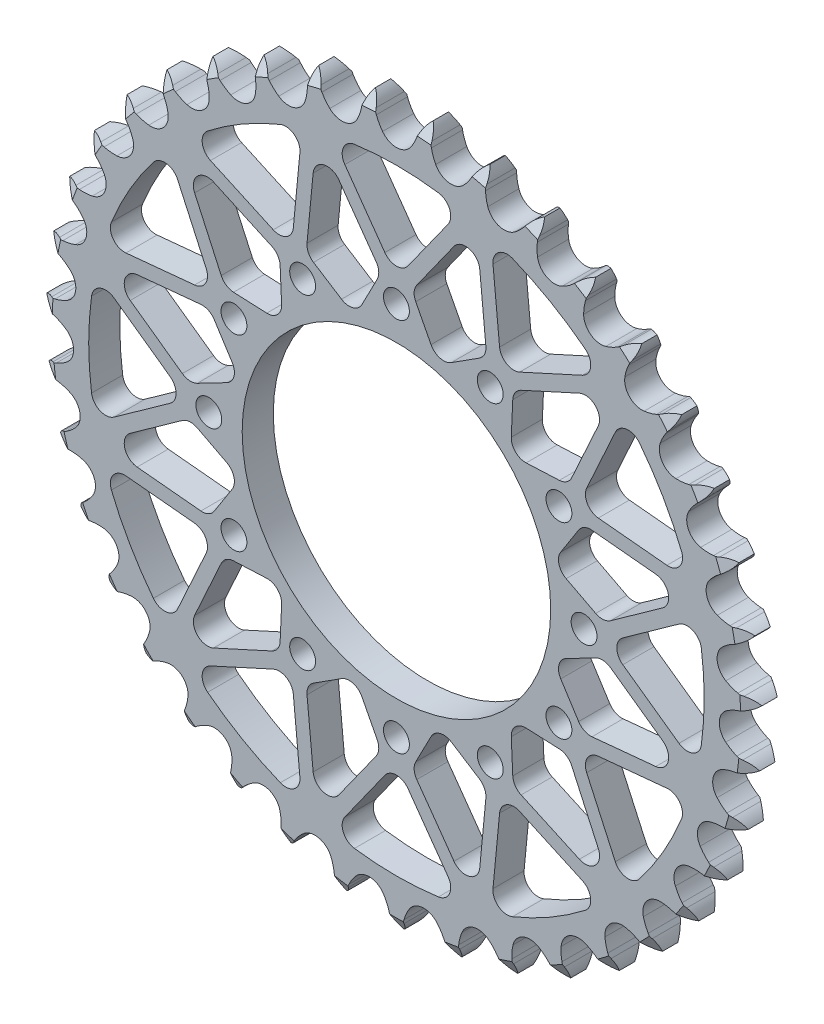
SolidWorks part; units mm, degrees
material "7075-T6 (SN)"
ref_plane "Front Plane" through (0, 0, 0) normal (0, 0, 1) x (1, 0, 0)
ref_plane "Top Plane" through (0, 0, 0) normal (0, 1, 0) x (1, 0, 0)
ref_plane "Right Plane" through (0, 0, 0) normal (1, 0, 0) x (0, 0, -1)
sketch "Work Sketch" plane through (0, 0, 0) normal (0, 0, 1) x (1, 0, 0)
  line L0 (0, 0) -> (0, 160.4542) construction
  line L1 (-112.0919, 78.9148) -> (87.2579, 78.9148) construction
  line L2 (5.102, 120.8822) -> (5.102, 112.9699) construction
  line L3 (-12.8497, 82.6953) -> (16.7256, 82.6953) construction
  line L4 (5.102, 82.6953) -> (-6.0879, 74.4036) construction
  line L5 (5.102, 82.6953) -> (-4.6505, 79.1506) construction
  line L6 (-4.6505, 79.1506) -> (-6.8863, 85.3019)
  line L7 (-11.5114, 78.0206) -> (-7.1525, 78.0206) construction
  line L8 (-11.0765, 124.7602) -> (-11.0765, 110.2345) construction
  line L9 (0, 0) -> (-3.4402, 42.6146) construction
  circle A0 centre (0, 0) radius 78.9148
  circle A1 centre (0, 78.9148) radius 4.0088
  arc A2 (-4.6505, 79.1506) -> (-3.2209, 76.5281) centre (5.0804, 82.7541) ccw
  circle A3 centre (-11.0765, 78.0206) radius 6.4254
  point P23 (-3.2209, 76.5281)
  dimension "D1" = 157.8295
  dimension "D8" = 10.3767
  dimension "D2" = 8.0177
  dimension "D3" = 5.102
  dimension "D4" = 3.7806
  dimension "D5" = 36.538
  dimension "D6" = 16.564
  dimension "D7" = 10.3767
  dimension "D9" = 0.8942
  dimension "D10" = 11.0765
  dimension "D11" = 4.615
sketch "Teeth Sketch" plane through (0, 0, 0) normal (0, 0, 1) x (1, 0, 0)
  line L0 (5.0376, 80.2155) -> (4.6505, 79.1506)
  line L1 (-7.4865, 92.7372) -> (-4.7839, 59.2593) construction
  line L2 (0, 0) -> (-10.9133, 132.3061) construction
  line L3 (7.8951, 79.9848) -> (8.1063, 78.8717)
  line L4 (16093.3137, -199351.4616) -> (-16096.7539, 199394.0762) construction
  line L5 (0, 146.3285) -> (0, 56.9858) construction
  line L6 (17.8398, 78.3686) -> (17.287, 77.3797)
  line L7 (0, -200000) -> (0, 200160.4542) construction
  line L8 (20.6234, 77.6826) -> (20.6533, 76.5499)
  line L9 (-4.6505, 79.1506) -> (-6.8863, 85.3019) construction
  line L10 (44.1616, 67.154) -> (43.8313, 66.0702)
  line L11 (-5.0376, 80.2155) -> (-4.6505, 79.1506)
  line L12 (30.18, 74.4921) -> (29.4757, 73.6046)
  line L13 (32.8175, 73.3684) -> (32.6653, 72.2456)
  line L14 (41.7385, 68.6862) -> (40.901, 67.9232)
  line L15 (52.2161, 61.1014) -> (51.267, 60.4826)
  line L16 (54.362, 59.2003) -> (53.8621, 58.1836)
  line L17 (61.3413, 51.9341) -> (60.3052, 51.4756)
  line L18 (63.1544, 49.7134) -> (62.4979, 48.79)
  line L19 (68.8777, 41.4218) -> (67.7815, 41.1354)
  line L20 (70.3112, 38.939) -> (69.515, 38.1328)
  line L21 (74.6303, 29.8366) -> (73.5023, 29.7298)
  line L22 (75.6469, 27.156) -> (74.7318, 26.488)
  line L23 (78.45, 17.4787) -> (77.3195, 17.5542)
  line L24 (79.0234, 14.6698) -> (78.013, 14.1572)
  line L25 (80.2378, 4.6681) -> (79.1341, 4.9239)
  line L26 (80.3533, 1.8035) -> (79.2737, 1.4597)
  line L27 (79.9476, -8.2634) -> (78.8992, -7.8338)
  line L28 (79.602, -11.1094) -> (78.4813, -11.2756)
  line L29 (77.5867, -20.9809) -> (76.6208, -20.3887)
  line L30 (76.7891, -23.7346) -> (75.6562, -23.7189)
  line L31 (73.2164, -33.155) -> (72.358, -32.4155)
  line L32 (71.9874, -35.7451) -> (70.8717, -35.5478)
  line L33 (66.9499, -44.4704) -> (66.2212, -43.6028)
  line L34 (65.3213, -46.8298) -> (64.2517, -46.4561)
  line L35 (58.9493, -54.634) -> (58.3693, -53.6608)
  line L36 (56.9634, -56.7016) -> (55.9676, -56.1612)
  line L37 (49.422, -63.3827) -> (49.0056, -62.329)
  line L38 (47.1301, -65.1049) -> (46.2339, -64.4118)
  line L39 (38.6147, -70.4897) -> (38.3727, -69.3829)
  line L40 (36.0763, -71.822) -> (35.3028, -70.9941)
  line L41 (26.8073, -75.7712) -> (26.746, -74.6398)
  line L42 (24.088, -76.679) -> (23.4574, -75.7377)
  line L43 (14.3056, -79.0901) -> (14.4266, -77.9636)
  line L44 (11.4759, -79.55) -> (11.0044, -78.5198)
  line L45 (1.4334, -80.3607) -> (1.7335, -79.2682)
  line L46 (-1.4334, -80.3607) -> (-1.7335, -79.2682)
  line L47 (-11.4759, -79.55) -> (-11.0044, -78.5198)
  line L48 (-14.3056, -79.0901) -> (-14.4266, -77.9636)
  line L49 (-24.088, -76.679) -> (-23.4574, -75.7377)
  line L50 (-26.8073, -75.7712) -> (-26.746, -74.6398)
  line L51 (-36.0763, -71.822) -> (-35.3028, -70.9941)
  line L52 (-38.6147, -70.4897) -> (-38.3727, -69.3829)
  line L53 (-47.1301, -65.1049) -> (-46.2339, -64.4118)
  line L54 (-49.422, -63.3827) -> (-49.0056, -62.329)
  line L55 (-56.9634, -56.7016) -> (-55.9676, -56.1612)
  line L56 (-58.9493, -54.634) -> (-58.3693, -53.6608)
  line L57 (-65.3213, -46.8298) -> (-64.2517, -46.4561)
  line L58 (-66.9499, -44.4704) -> (-66.2212, -43.6028)
  line L59 (-71.9874, -35.7451) -> (-70.8717, -35.5478)
  line L60 (-73.2164, -33.155) -> (-72.358, -32.4155)
  line L61 (-76.7891, -23.7346) -> (-75.6562, -23.7189)
  line L62 (-77.5867, -20.9809) -> (-76.6208, -20.3887)
  line L63 (-79.602, -11.1094) -> (-78.4813, -11.2756)
  line L64 (-79.9476, -8.2634) -> (-78.8992, -7.8338)
  line L65 (-80.3533, 1.8035) -> (-79.2737, 1.4597)
  line L66 (-80.2378, 4.6681) -> (-79.1341, 4.9239)
  line L67 (-79.0234, 14.6698) -> (-78.013, 14.1572)
  line L68 (-78.45, 17.4787) -> (-77.3195, 17.5542)
  line L69 (-75.6469, 27.156) -> (-74.7318, 26.488)
  line L70 (-74.6303, 29.8366) -> (-73.5023, 29.7298)
  line L71 (-70.3112, 38.939) -> (-69.515, 38.1328)
  line L72 (-68.8777, 41.4218) -> (-67.7815, 41.1354)
  line L73 (-63.1544, 49.7134) -> (-62.4979, 48.79)
  line L74 (-61.3413, 51.9341) -> (-60.3052, 51.4756)
  line L75 (-54.362, 59.2003) -> (-53.8621, 58.1836)
  line L76 (-52.2161, 61.1014) -> (-51.267, 60.4826)
  line L77 (-44.1616, 67.154) -> (-43.8313, 66.0702)
  line L78 (-41.7385, 68.6862) -> (-40.901, 67.9232)
  line L79 (-32.8175, 73.3684) -> (-32.6653, 72.2456)
  line L80 (-30.18, 74.4921) -> (-29.4757, 73.6046)
  line L81 (-20.6234, 77.6826) -> (-20.6533, 76.5499)
  line L82 (-17.8398, 78.3686) -> (-17.287, 77.3797)
  line L83 (-7.8951, 79.9848) -> (-8.1063, 78.8717)
  arc A0 (-6.8336, 82.8459) -> (-5.0376, 80.2155) centre (-11.0765, 78.0206) cw
  circle A1 centre (-11.0765, 78.0206) radius 6.4254 construction
  arc A2 (-3.2209, 76.5281) -> (-4.6505, 79.1506) centre (5.0804, 82.7541) cw
  arc A3 (-4.6505, 79.1506) -> (-3.2209, 76.5281) centre (5.0804, 82.7541) ccw construction
  circle A4 centre (0, 78.9148) radius 4.0088 construction
  arc A5 (-3.2209, 76.5281) -> (3.2209, 76.5281) centre (0, 78.9148) ccw
  arc A6 (3.2209, 76.5281) -> (4.6505, 79.1506) centre (-5.0804, 82.7541) ccw
  arc A7 (6.8336, 82.8459) -> (5.0376, 80.2155) centre (11.0765, 78.0206) ccw
  arc A8 (6.5443, 82.8692) -> (7.8951, 79.9848) centre (1.5824, 78.787) cw
  arc A9 (9.0967, 76.0537) -> (8.1063, 78.8717) centre (18.2893, 80.8676) cw
  arc A10 (9.0967, 76.0537) -> (15.4552, 75.0204) centre (12.6588, 77.8928) ccw
  arc A11 (15.4552, 75.0204) -> (17.287, 77.3797) centre (8.2601, 82.4975) ccw
  arc A12 (20.0345, 80.6769) -> (17.8398, 78.3686) centre (23.4484, 75.2334) ccw
  arc A13 (19.7528, 80.7463) -> (20.6234, 77.6826) centre (14.2002, 77.5129) cw
  arc A14 (21.1788, 73.6096) -> (20.6533, 76.5499) centre (31.0245, 76.8865) cw
  arc A15 (21.1788, 73.6096) -> (27.2892, 71.5697) centre (24.9898, 74.8535) ccw
  arc A16 (27.2892, 71.5697) -> (29.4757, 73.6046) centre (21.3867, 80.1041) ccw
  arc A17 (32.7165, 76.4184) -> (30.18, 74.4921) centre (35.2131, 70.4978) ccw
  arc A18 (32.4496, 76.5321) -> (32.8175, 73.3684) centre (26.4502, 74.2313) cw
  arc A19 (32.7124, 69.2591) -> (32.6653, 72.2456) centre (42.9562, 70.9142) cw
  arc A20 (32.7124, 69.2591) -> (38.4163, 66.2654) centre (36.6735, 69.8756) ccw
  arc A21 (38.4163, 66.2654) -> (40.901, 67.9232) centre (33.9593, 75.6361) ccw
  arc A22 (44.5512, 70.1807) -> (41.7385, 68.6862) centre (46.0657, 63.9363) ccw
  arc A23 (44.306, 70.3358) -> (44.1616, 67.154) centre (38.0153, 69.0271) cw
  arc A24 (43.3987, 63.1147) -> (43.8313, 66.0702) centre (53.7754, 63.1052) cw
  arc A25 (43.3987, 63.1147) -> (48.5486, 59.2448) centre (47.4074, 63.0878) ccw
  arc A26 (48.5486, 59.2448) -> (51.267, 60.4826) centre (45.6524, 69.2092) ccw
  arc A27 (55.2321, 62.1253) -> (52.2161, 61.1014) centre (55.7253, 55.7189) ccw
  arc A28 (55.0149, 62.3178) -> (54.362, 59.2003) centre (48.5957, 62.0351) cw
  arc A29 (52.961, 55.3358) -> (53.8621, 58.1836) centre (63.2018, 53.6618) cw
  arc A30 (52.961, 55.3358) -> (57.4234, 50.6899) centre (56.9135, 54.6662) ccw
  arc A31 (57.4234, 50.6899) -> (60.3052, 51.4756) centre (56.1632, 60.9898) ccw
  arc A32 (64.4824, 52.461) -> (61.3413, 51.9341) centre (63.9416, 46.0584) ccw
  arc A33 (64.2989, 52.6858) -> (63.1544, 49.7134) centre (57.9175, 53.4365) cw
  arc A34 (61.1517, 46.1237) -> (62.4979, 48.79) centre (70.9913, 42.8287) cw
  arc A35 (61.1517, 46.1237) -> (64.811, 40.8221) centre (64.9456, 44.8287) ccw
  arc A36 (64.811, 40.8221) -> (67.7815, 41.1354) centre (65.2193, 51.1908) ccw
  arc A37 (72.0627, 41.4379) -> (68.8777, 41.4218) centre (70.5018, 35.205) ccw
  arc A38 (71.9177, 41.6892) -> (70.3112, 38.939) centre (65.7393, 43.4539) cw
  arc A39 (67.7585, 35.717) -> (69.515, 38.1328) centre (76.9422, 30.8862) cw
  arc A40 (67.7585, 35.717) -> (70.5201, 29.8971) centre (71.2956, 33.8302) ccw
  arc A41 (70.5201, 29.8971) -> (73.5023, 29.7298) centre (72.5864, 40.0659) ccw
  arc A42 (77.7767, 29.3416) -> (74.6303, 29.8366) centre (75.2361, 23.4398) ccw
  arc A43 (77.6738, 29.6129) -> (75.6469, 27.156) centre (71.8585, 32.3458) cw
  arc A44 (72.6105, 24.3852) -> (74.7318, 26.488) centre (80.9003, 18.1439) cw
  arc A45 (72.6105, 24.3852) -> (74.4027, 18.1977) centre (75.7991, 21.9555) ccw
  arc A46 (74.4027, 18.1977) -> (77.3195, 17.5542) centre (78.0734, 27.9034) ccw
  arc A47 (81.4762, 16.4854) -> (78.45, 17.4787) centre (78.0218, 11.0675) ccw
  arc A48 (81.4182, 16.7697) -> (79.0234, 14.6698) centre (76.1166, 20.4) cw
  arc A49 (75.5818, 12.4219) -> (78.013, 14.1572) centre (82.7631, 4.9316) cw
  arc A50 (75.5818, 12.4219) -> (76.3583, 6.027) centre (78.3394, 9.5121) ccw
  arc A51 (76.3583, 6.027) -> (79.1341, 4.9239) centre (81.5384, 15.0182) ccw
  arc A52 (83.0656, 3.2022) -> (80.2378, 4.6681) centre (78.7868, -1.5914) ccw
  arc A53 (83.0539, 3.4922) -> (80.3533, 1.8035) centre (78.4033, 7.9259) cw
  arc A54 (76.5957, 0.1368) -> (79.2737, 1.4597) centre (82.4825, -8.4084) cw
  arc A55 (76.5957, 0.1368) -> (76.3363, -6.2998) centre (78.8508, -3.1776) ccw
  arc A56 (76.3363, -6.2998) -> (78.8992, -7.8338) centre (82.8916, 1.7441) ccw
  arc A57 (82.5035, -10.1639) -> (79.9476, -8.2634) centre (77.5113, -14.2091) ccw
  arc A58 (82.5385, -9.8758) -> (79.602, -11.1094) centre (78.6594, -4.7535) cw
  arc A59 (75.6257, -12.1517) -> (78.4813, -11.2756) centre (80.0655, -21.5307) cw
  arc A60 (75.6257, -12.1517) -> (74.3372, -18.4634) centre (77.3199, -15.785) ccw
  arc A61 (74.3372, -18.4634) -> (76.6208, -20.3887) centre (82.0979, -11.5753) ccw
  arc A62 (79.8047, -23.2668) -> (77.5867, -20.9809) centre (74.2283, -26.4587) ccw
  arc A63 (79.8855, -22.9881) -> (76.7891, -23.7346) centre (76.8783, -17.3098) cw
  arc A64 (72.6971, -24.1256) -> (75.6562, -23.7189) centre (75.5749, -34.0953) cw
  arc A65 (72.6971, -24.1256) -> (70.4128, -30.1488) centre (73.7866, -27.9836) ccw
  arc A66 (70.4128, -30.1488) -> (72.358, -32.4155) centre (79.178, -24.5948) ccw
  arc A67 (75.039, -35.7671) -> (73.2164, -33.155) centre (69.0227, -38.0232) ccw
  arc A68 (75.1634, -35.5049) -> (71.9874, -35.7451) centre (73.106, -29.4178) cw
  arc A69 (67.8857, -35.4746) -> (70.8717, -35.5478) centre (69.127, -45.7768) cw
  arc A70 (67.8857, -35.4746) -> (64.6648, -41.0534) centre (68.3422, -39.4574) ccw
  arc A71 (64.6648, -41.0534) -> (66.2212, -43.6028) centre (74.2074, -36.9773) ccw
  arc A72 (68.3299, -47.341) -> (66.9499, -44.4704) centre (62.0296, -48.6028) ccw
  arc A73 (68.4947, -47.1022) -> (65.3213, -46.8298) centre (67.4404, -40.7639) cw
  arc A74 (61.3161, -45.9049) -> (64.2517, -46.4561) centre (60.8887, -56.2728) cw
  arc A75 (61.3161, -45.9049) -> (57.2419, -50.8948) centre (61.1278, -49.9093) ccw
  arc A76 (57.2419, -50.8948) -> (58.3693, -53.6608) centre (67.3148, -48.4022) ccw
  arc A77 (59.851, -57.6888) -> (58.9493, -54.634) centre (53.4299, -57.9236) ccw
  arc A78 (60.052, -57.4796) -> (56.9634, -56.7016) centre (60.0281, -51.0542) cw
  arc A79 (53.1584, -55.1462) -> (55.9676, -56.1612) centre (51.0734, -65.3113) cw
  arc A80 (53.1584, -55.1462) -> (48.3366, -59.4179) centre (52.3302, -59.0685) ccw
  arc A81 (48.3366, -59.4179) -> (49.0056, -62.329) centre (58.6789, -58.5735) ccw
  arc A82 (49.822, -66.5425) -> (49.422, -63.3827) centre (43.4464, -65.7443) ccw
  arc A83 (50.054, -66.3682) -> (47.1301, -65.1049) centre (51.0611, -60.0222) cw
  arc A84 (43.6239, -62.9593) -> (46.2339, -64.4118) centre (39.9354, -72.6583) cw
  arc A85 (43.6239, -62.9593) -> (38.1793, -66.4022) centre (42.1772, -66.698) ccw
  arc A86 (38.1793, -66.4022) -> (38.3727, -69.3829) centre (48.5231, -67.2277) ccw
  arc A87 (38.5026, -73.6728) -> (38.6147, -70.4897) centre (32.3376, -71.8622) ccw
  arc A88 (38.7596, -73.538) -> (36.0763, -71.822) centre (40.7716, -67.4357) cw
  arc A89 (32.9596, -69.1417) -> (35.3028, -70.9941) centre (27.763, -78.1234) cw
  arc A90 (32.9596, -69.1417) -> (27.0333, -71.6667) centre (30.932, -72.6) ccw
  arc A91 (27.0333, -71.6667) -> (26.746, -74.6398) centre (37.1107, -74.1408) ccw
  arc A92 (26.1861, -78.8951) -> (26.8073, -75.7712) centre (20.3913, -76.1189) ccw
  arc A93 (26.4613, -78.8032) -> (24.088, -76.679) centre (29.4261, -73.1027) cw
  arc A94 (21.4417, -73.5335) -> (23.4574, -75.7377) centre (14.8716, -81.5653) cw
  arc A95 (21.4417, -73.5335) -> (15.187, -75.0751) centre (18.8855, -76.6216) ccw
  arc A96 (15.187, -75.0751) -> (14.4266, -77.9636) centre (24.7371, -79.1336) ccw
  arc A97 (13.1913, -82.0739) -> (14.3056, -79.0901) centre (7.9169, -78.4042) ccw
  arc A98 (13.4777, -82.0274) -> (11.4759, -79.55) centre (17.3186, -76.8763) cw
  arc A99 (9.3684, -76.0207) -> (11.0044, -78.5198) centre (1.595, -82.8946) cw
  arc A100 (9.3684, -76.0207) -> (2.9475, -76.5391) centre (6.35, -78.6589) ccw
  arc A101 (2.9475, -76.5391) -> (1.7335, -79.2682) centre (11.7228, -82.077) ccw
  arc A102 (-0.1451, -83.1271) -> (1.4334, -80.3607) centre (-4.7625, -78.6589) ccw
  arc A103 (0.1451, -83.1271) -> (-1.4334, -80.3607) centre (4.7625, -78.6589) cw
  arc A104 (-2.9475, -76.5391) -> (-1.7335, -79.2682) centre (-11.7228, -82.077) cw
  arc A105 (-2.9475, -76.5391) -> (-9.3684, -76.0207) centre (-6.35, -78.6589) ccw
  arc A106 (-9.3684, -76.0207) -> (-11.0044, -78.5198) centre (-1.595, -82.8946) ccw
  arc A107 (-13.4777, -82.0274) -> (-11.4759, -79.55) centre (-17.3186, -76.8763) ccw
  arc A108 (-13.1913, -82.0739) -> (-14.3056, -79.0901) centre (-7.9169, -78.4042) cw
  arc A109 (-15.187, -75.0751) -> (-14.4266, -77.9636) centre (-24.7371, -79.1336) cw
  arc A110 (-15.187, -75.0751) -> (-21.4417, -73.5335) centre (-18.8855, -76.6216) ccw
  arc A111 (-21.4417, -73.5335) -> (-23.4574, -75.7377) centre (-14.8716, -81.5653) ccw
  arc A112 (-26.4613, -78.8032) -> (-24.088, -76.679) centre (-29.4261, -73.1027) ccw
  arc A113 (-26.1861, -78.8951) -> (-26.8073, -75.7712) centre (-20.3913, -76.1189) cw
  arc A114 (-27.0333, -71.6667) -> (-26.746, -74.6398) centre (-37.1107, -74.1408) cw
  arc A115 (-27.0333, -71.6667) -> (-32.9596, -69.1417) centre (-30.932, -72.6) ccw
  arc A116 (-32.9596, -69.1417) -> (-35.3028, -70.9941) centre (-27.763, -78.1234) ccw
  arc A117 (-38.7596, -73.538) -> (-36.0763, -71.822) centre (-40.7716, -67.4357) ccw
  arc A118 (-38.5026, -73.6728) -> (-38.6147, -70.4897) centre (-32.3376, -71.8622) cw
  arc A119 (-38.1793, -66.4022) -> (-38.3727, -69.3829) centre (-48.5231, -67.2277) cw
  arc A120 (-38.1793, -66.4022) -> (-43.6239, -62.9593) centre (-42.1772, -66.698) ccw
  arc A121 (-43.6239, -62.9593) -> (-46.2339, -64.4118) centre (-39.9354, -72.6583) ccw
  arc A122 (-50.054, -66.3682) -> (-47.1301, -65.1049) centre (-51.0611, -60.0222) ccw
  arc A123 (-49.822, -66.5425) -> (-49.422, -63.3827) centre (-43.4464, -65.7443) cw
  arc A124 (-48.3366, -59.4179) -> (-49.0056, -62.329) centre (-58.6789, -58.5735) cw
  arc A125 (-48.3366, -59.4179) -> (-53.1584, -55.1462) centre (-52.3302, -59.0685) ccw
  arc A126 (-53.1584, -55.1462) -> (-55.9676, -56.1612) centre (-51.0734, -65.3113) ccw
  arc A127 (-60.052, -57.4796) -> (-56.9634, -56.7016) centre (-60.0281, -51.0542) ccw
  arc A128 (-59.851, -57.6888) -> (-58.9493, -54.634) centre (-53.4299, -57.9236) cw
  arc A129 (-57.2419, -50.8948) -> (-58.3693, -53.6608) centre (-67.3148, -48.4022) cw
  arc A130 (-57.2419, -50.8948) -> (-61.3161, -45.9049) centre (-61.1278, -49.9093) ccw
  arc A131 (-61.3161, -45.9049) -> (-64.2517, -46.4561) centre (-60.8887, -56.2728) ccw
  arc A132 (-68.4947, -47.1022) -> (-65.3213, -46.8298) centre (-67.4404, -40.7639) ccw
  arc A133 (-68.3299, -47.341) -> (-66.9499, -44.4704) centre (-62.0296, -48.6028) cw
  arc A134 (-64.6648, -41.0534) -> (-66.2212, -43.6028) centre (-74.2074, -36.9773) cw
  arc A135 (-64.6648, -41.0534) -> (-67.8857, -35.4746) centre (-68.3422, -39.4574) ccw
  arc A136 (-67.8857, -35.4746) -> (-70.8717, -35.5478) centre (-69.127, -45.7768) ccw
  arc A137 (-75.1634, -35.5049) -> (-71.9874, -35.7451) centre (-73.106, -29.4178) ccw
  arc A138 (-75.039, -35.7671) -> (-73.2164, -33.155) centre (-69.0227, -38.0232) cw
  arc A139 (-70.4128, -30.1488) -> (-72.358, -32.4155) centre (-79.178, -24.5948) cw
  arc A140 (-70.4128, -30.1488) -> (-72.6971, -24.1256) centre (-73.7866, -27.9836) ccw
  arc A141 (-72.6971, -24.1256) -> (-75.6562, -23.7189) centre (-75.5749, -34.0953) ccw
  arc A142 (-79.8855, -22.9881) -> (-76.7891, -23.7346) centre (-76.8783, -17.3098) ccw
  arc A143 (-79.8047, -23.2668) -> (-77.5867, -20.9809) centre (-74.2283, -26.4587) cw
  arc A144 (-74.3372, -18.4634) -> (-76.6208, -20.3887) centre (-82.0979, -11.5753) cw
  arc A145 (-74.3372, -18.4634) -> (-75.6257, -12.1517) centre (-77.3199, -15.785) ccw
  arc A146 (-75.6257, -12.1517) -> (-78.4813, -11.2756) centre (-80.0655, -21.5307) ccw
  arc A147 (-82.5385, -9.8758) -> (-79.602, -11.1094) centre (-78.6594, -4.7535) ccw
  arc A148 (-82.5035, -10.1639) -> (-79.9476, -8.2634) centre (-77.5113, -14.2091) cw
  arc A149 (-76.3363, -6.2998) -> (-78.8992, -7.8338) centre (-82.8916, 1.7441) cw
  arc A150 (-76.3363, -6.2998) -> (-76.5957, 0.1368) centre (-78.8508, -3.1776) ccw
  arc A151 (-76.5957, 0.1368) -> (-79.2737, 1.4597) centre (-82.4825, -8.4084) ccw
  arc A152 (-83.0539, 3.4922) -> (-80.3533, 1.8035) centre (-78.4033, 7.9259) ccw
  arc A153 (-83.0656, 3.2022) -> (-80.2378, 4.6681) centre (-78.7868, -1.5914) cw
  arc A154 (-76.3583, 6.027) -> (-79.1341, 4.9239) centre (-81.5384, 15.0182) cw
  arc A155 (-76.3583, 6.027) -> (-75.5818, 12.4219) centre (-78.3394, 9.5121) ccw
  arc A156 (-75.5818, 12.4219) -> (-78.013, 14.1572) centre (-82.7631, 4.9316) ccw
  arc A157 (-81.4182, 16.7697) -> (-79.0234, 14.6698) centre (-76.1166, 20.4) ccw
  arc A158 (-81.4762, 16.4854) -> (-78.45, 17.4787) centre (-78.0218, 11.0675) cw
  arc A159 (-74.4027, 18.1977) -> (-77.3195, 17.5542) centre (-78.0734, 27.9034) cw
  arc A160 (-74.4027, 18.1977) -> (-72.6105, 24.3852) centre (-75.7991, 21.9555) ccw
  arc A161 (-72.6105, 24.3852) -> (-74.7318, 26.488) centre (-80.9003, 18.1439) ccw
  arc A162 (-77.6738, 29.6129) -> (-75.6469, 27.156) centre (-71.8585, 32.3458) ccw
  arc A163 (-77.7767, 29.3416) -> (-74.6303, 29.8366) centre (-75.2361, 23.4398) cw
  arc A164 (-70.5201, 29.8971) -> (-73.5023, 29.7298) centre (-72.5864, 40.0659) cw
  arc A165 (-70.5201, 29.8971) -> (-67.7585, 35.717) centre (-71.2956, 33.8302) ccw
  arc A166 (-67.7585, 35.717) -> (-69.515, 38.1328) centre (-76.9422, 30.8862) ccw
  arc A167 (-71.9177, 41.6892) -> (-70.3112, 38.939) centre (-65.7393, 43.4539) ccw
  arc A168 (-72.0627, 41.4379) -> (-68.8777, 41.4218) centre (-70.5018, 35.205) cw
  arc A169 (-64.811, 40.8221) -> (-67.7815, 41.1354) centre (-65.2193, 51.1908) cw
  arc A170 (-64.811, 40.8221) -> (-61.1517, 46.1237) centre (-64.9456, 44.8287) ccw
  arc A171 (-61.1517, 46.1237) -> (-62.4979, 48.79) centre (-70.9913, 42.8287) ccw
  arc A172 (-64.2989, 52.6858) -> (-63.1544, 49.7134) centre (-57.9175, 53.4365) ccw
  arc A173 (-64.4824, 52.461) -> (-61.3413, 51.9341) centre (-63.9416, 46.0584) cw
  arc A174 (-57.4234, 50.6899) -> (-60.3052, 51.4756) centre (-56.1632, 60.9898) cw
  arc A175 (-57.4234, 50.6899) -> (-52.961, 55.3358) centre (-56.9135, 54.6662) ccw
  arc A176 (-52.961, 55.3358) -> (-53.8621, 58.1836) centre (-63.2018, 53.6618) ccw
  arc A177 (-55.0149, 62.3178) -> (-54.362, 59.2003) centre (-48.5957, 62.0351) ccw
  arc A178 (-55.2321, 62.1253) -> (-52.2161, 61.1014) centre (-55.7253, 55.7189) cw
  arc A179 (-48.5486, 59.2448) -> (-51.267, 60.4826) centre (-45.6524, 69.2092) cw
  arc A180 (-48.5486, 59.2448) -> (-43.3987, 63.1147) centre (-47.4074, 63.0878) ccw
  arc A181 (-43.3987, 63.1147) -> (-43.8313, 66.0702) centre (-53.7754, 63.1052) ccw
  arc A182 (-44.306, 70.3358) -> (-44.1616, 67.154) centre (-38.0153, 69.0271) ccw
  arc A183 (-44.5512, 70.1807) -> (-41.7385, 68.6862) centre (-46.0657, 63.9363) cw
  arc A184 (-38.4163, 66.2654) -> (-40.901, 67.9232) centre (-33.9593, 75.6361) cw
  arc A185 (-38.4163, 66.2654) -> (-32.7124, 69.2591) centre (-36.6735, 69.8756) ccw
  arc A186 (-32.7124, 69.2591) -> (-32.6653, 72.2456) centre (-42.9562, 70.9142) ccw
  arc A187 (-32.4496, 76.5321) -> (-32.8175, 73.3684) centre (-26.4502, 74.2313) ccw
  arc A188 (-32.7165, 76.4184) -> (-30.18, 74.4921) centre (-35.2131, 70.4978) cw
  arc A189 (-27.2892, 71.5697) -> (-29.4757, 73.6046) centre (-21.3867, 80.1041) cw
  arc A190 (-27.2892, 71.5697) -> (-21.1788, 73.6096) centre (-24.9898, 74.8535) ccw
  arc A191 (-21.1788, 73.6096) -> (-20.6533, 76.5499) centre (-31.0245, 76.8865) ccw
  arc A192 (-19.7528, 80.7463) -> (-20.6234, 77.6826) centre (-14.2002, 77.5129) ccw
  arc A193 (-20.0345, 80.6769) -> (-17.8398, 78.3686) centre (-23.4484, 75.2334) cw
  arc A194 (-15.4552, 75.0204) -> (-17.287, 77.3797) centre (-8.2601, 82.4975) cw
  arc A195 (-15.4552, 75.0204) -> (-9.0967, 76.0537) centre (-12.6588, 77.8928) ccw
  arc A196 (-9.0967, 76.0537) -> (-8.1063, 78.8717) centre (-18.2893, 80.8676) ccw
  arc A197 (-6.5443, 82.8692) -> (-7.8951, 79.9848) centre (-1.5824, 78.787) ccw
  point P77 (0, 0)
  dimension "D1" = 4.615
  dimension "D2" = 4.715
  dimension "D3" = 39
extrude "Extrusion" add sketch "Teeth Sketch" along normal blind 7.2136 contours A0 region at (0, 0, 0)
sketch "Sketch1" plane through (0, 0, 0) normal (0, 0, -1) x (-1, 0, 0)
  circle A0 centre (0, 0) radius 78.9443
  circle A1 centre (0, 0) radius 35.7643
  dimension "D1" = 43.18
extrude "Cut-Extrude" cut sketch "Sketch1" against normal through all both and the other way through all contours A1
ref_axis "Axis2" through (0, 0, -0.3607) along (0, 0, 1)
ref_axis "Axis1" [suppressed] through (0, 0, 7.2136) along (0, 0, -1)
ref_plane "Sprocket Center Plane" through (0, 0, 3.6068) normal (0, 0, 1) x (1, 0, 0)
sketch "Pitch Circle" plane through (0, 0, 3.6068) normal (0, 0, -1) x (-1, 0, 0)
  circle A0 centre (0, 0) radius 82.9531 construction
  dimension "D1" = 165.9063
sketch "Chain Pitch Circle" plane through (0, 0, 0) normal (0, 0, -1) x (-1, 0, 0)
  circle A0 centre (0, 0) radius 82.9531 construction
  dimension "D1" = 165.9063
ref_plane "Center Plane" through (0, 0, 3.6068) normal (0, 0, 1) x (1, 0, 0)
hole_wizard "Ø6.0mm Dowel Hole1" positions "Sketch7" profile "Sketch8" hole size "Ø6.0" standard "ANSI Metric" end condition through all
sketch "Sketch7" plane through (0, 0, 7.2136) normal (0, 0, 1) x (1, 0, 0)
  point P0 (-43.5, 0)
  dimension "D1" = 43.5
sketch "Sketch8" plane through (-43.5, 0, 7.2136) normal (1, 0, 0) x (0, -1, 0)
  line L0 (0, 0) -> (0, 7.2136)
  line L1 (0, 7.2136) -> (3, 7.2136)
  line L2 (3, 7.2136) -> (3, 0)
  line L5 (3, 0) -> (0, 0)
  line L11 (0, -6.35) -> (0, 107.95) construction
  dimension "Thru Hole Dia." = 6
  dimension "Thru Hole Depth" = 7.2136
pattern_circular "CirPattern1" count 12 over 360 about axis through (0, 0, 7.2136) along (0, 0, -1) of "Ø6.0mm Dowel Hole1" reverse direction yes
ref_plane "Plane1" through (0, 0, 3.6068) normal (0, 0, -1) x (-1, 0, 0)
sketch "Sketch9" plane through (0, 0, 0) normal (0, 0, 1) x (1, 0, 0)
  line L0 (-43.5, 0) -> (-71.3499, 0) construction
  line L1 (-69.7539, 15.0068) -> (-48.707, 0)
  line L2 (-69.7539, -15.0068) -> (-48.707, 0)
  line L11 (-43.5, 0) -> (-37.6721, 21.75) construction
  line L13 (-68.9187, 18.4667) -> (-36.1404, 9.6838) construction
  line L18 (-43.3252, 20.9264) -> (-36.1404, 9.6838)
  line L19 (-47.9839, 3.5399) -> (-36.1404, 9.6838)
  line L20 (-43.3252, 20.9264) -> (-68.9187, 18.4667)
  line L21 (-47.9839, 3.5399) -> (-68.9187, 18.4667)
  circle A0 centre (0, 0) radius 74.9059 construction
  arc A1 (-57.4234, 50.6899) -> (-52.961, 55.3358) centre (-56.9135, 54.6662) ccw construction
  circle A2 centre (-43.5, 0) radius 3 construction
  circle A3 centre (-43.5, 0) radius 5.207
  circle A4 centre (-37.6721, 21.75) radius 3 construction
  circle A6 centre (-37.6721, 21.75) radius 5.207
  circle A196 centre (0, 0) radius 71.3499
  circle A197 centre (0, 0) radius 35.7643 construction
  circle A198 centre (0, 0) radius 35.7643
  circle A199 centre (0, 0) radius 37.4153 construction
  point P17 (-40.5861, 10.875)
  dimension "D1" = 3.556
  dimension "D2" = 1.651
  dimension "D3" = 10.414
  dimension "D4" = 3.302
extrude "Cut-Extrude2" cut sketch "Sketch9" along normal through all contours L1 A196 L2 | L21 L19 L18 L20 region at (-63.4426, 0, 0) region at (-50.2379, 13.4612, 0)
fillet "Fillet2" radius 3.302 7 edges at (-68.9187, 18.4667, 3.6068) (-36.1404, 9.6838, 3.6068) (-47.9839, 3.5399, 3.6068) (-43.3252, 20.9264, 3.6068) (-69.7539, -15.0068, 3.6068) (-48.707, 0, 3.6068) (-69.7539, 15.0068, 3.6068)
pattern_circular "CirPattern3" count 12 over 360 about axis through (0, 0, 7.2136) along (0, 0, -1) of "Cut-Extrude2", "Fillet2"
sketch "Sketch14" plane through (0, 0, 7.2136) normal (0, 0, 1) x (1, 0, 0)
  line L0 (-46.191, -4.47) -> (-39.3483, -8.0197) construction
  line L1 (-38.2956, 5.9905) -> (-37.9766, 6.1559)
  line L2 (-43.5, 0) -> (-38.293, 0) construction
  line L3 (-38.2956, -5.9905) -> (-37.9766, -6.1559)
  line L4 (-30.1697, 24.3357) -> (-29.8108, 24.3195)
  line L5 (-36.1602, 13.9599) -> (-35.9667, 13.6571)
  line L6 (-13.9599, 36.1602) -> (-13.6571, 35.9667)
  line L7 (-24.3357, 30.1697) -> (-24.3195, 29.8108)
  line L8 (5.9905, 38.2956) -> (6.1559, 37.9766)
  line L9 (-5.9905, 38.2956) -> (-6.1559, 37.9766)
  line L10 (24.3357, 30.1697) -> (24.3195, 29.8108)
  line L11 (13.9599, 36.1602) -> (13.6571, 35.9667)
  line L12 (36.1602, 13.9599) -> (35.9667, 13.6571)
  line L13 (30.1697, 24.3357) -> (29.8108, 24.3195)
  line L14 (38.2956, -5.9905) -> (37.9766, -6.1559)
  line L15 (38.2956, 5.9905) -> (37.9766, 6.1559)
  line L16 (30.1697, -24.3357) -> (29.8108, -24.3195)
  line L17 (36.1602, -13.9599) -> (35.9667, -13.6571)
  line L18 (13.9599, -36.1602) -> (13.6571, -35.9667)
  line L19 (24.3357, -30.1697) -> (24.3195, -29.8108)
  line L20 (-5.9905, -38.2956) -> (-6.1559, -37.9766)
  line L21 (5.9905, -38.2956) -> (6.1559, -37.9766)
  line L22 (-24.3357, -30.1697) -> (-24.3195, -29.8108)
  line L23 (-13.9599, -36.1602) -> (-13.6571, -35.9667)
  line L24 (-36.1602, -13.9599) -> (-35.9667, -13.6571)
  line L25 (-30.1697, -24.3357) -> (-29.8108, -24.3195)
  arc A0 (-39.0014, -2.6222) -> (-39.0014, 2.6222) centre (-43.5, 0) ccw
  circle A1 centre (0, 0) radius 35.7643 construction
  arc A2 (-37.9766, -6.1559) -> (-39.0014, -2.6222) centre (-36.807, -3.9013) cw
  arc A3 (-38.2956, 5.9905) -> (-36.1602, 13.9599) centre (-40.8688, 10.9508) ccw
  arc A4 (-38.2956, 5.9905) -> (-36.1602, 13.9599) centre (-40.8688, 10.9508) ccw
  arc A5 (-37.9766, 6.1559) -> (-39.0014, 2.6222) centre (-36.807, 3.9013) ccw
  circle A6 centre (0, 0) radius 35.7643
  arc A7 (-30.1697, 24.3357) -> (-24.3357, 30.1697) centre (-29.918, 29.918) ccw
  arc A8 (-29.8108, 24.3195) -> (-32.4651, 21.7716) centre (-29.9252, 21.7821) ccw
  arc A9 (-35.0873, 17.2299) -> (-32.4651, 21.7716) centre (-37.6721, 21.75) ccw
  arc A10 (-35.9667, 13.6571) -> (-35.0873, 17.2299) centre (-33.8264, 15.0249) cw
  arc A11 (-13.9599, 36.1602) -> (-5.9905, 38.2956) centre (-10.9508, 40.8688) ccw
  arc A12 (-13.6571, 35.9667) -> (-17.2299, 35.0873) centre (-15.0249, 33.8264) ccw
  arc A13 (-21.7716, 32.4651) -> (-17.2299, 35.0873) centre (-21.75, 37.6721) ccw
  arc A14 (-24.3195, 29.8108) -> (-21.7716, 32.4651) centre (-21.7821, 29.9252) cw
  arc A15 (5.9905, 38.2956) -> (13.9599, 36.1602) centre (10.9508, 40.8688) ccw
  arc A16 (6.1559, 37.9766) -> (2.6222, 39.0014) centre (3.9013, 36.807) ccw
  arc A17 (-2.6222, 39.0014) -> (2.6222, 39.0014) centre (0, 43.5) ccw
  arc A18 (-6.1559, 37.9766) -> (-2.6222, 39.0014) centre (-3.9013, 36.807) cw
  arc A19 (24.3357, 30.1697) -> (30.1697, 24.3357) centre (29.918, 29.918) ccw
  arc A20 (24.3195, 29.8108) -> (21.7716, 32.4651) centre (21.7821, 29.9252) ccw
  arc A21 (17.2299, 35.0873) -> (21.7716, 32.4651) centre (21.75, 37.6721) ccw
  arc A22 (13.6571, 35.9667) -> (17.2299, 35.0873) centre (15.0249, 33.8264) cw
  arc A23 (36.1602, 13.9599) -> (38.2956, 5.9905) centre (40.8688, 10.9508) ccw
  arc A24 (35.9667, 13.6571) -> (35.0873, 17.2299) centre (33.8264, 15.0249) ccw
  arc A25 (32.4651, 21.7716) -> (35.0873, 17.2299) centre (37.6721, 21.75) ccw
  arc A26 (29.8108, 24.3195) -> (32.4651, 21.7716) centre (29.9252, 21.7821) cw
  arc A27 (38.2956, -5.9905) -> (36.1602, -13.9599) centre (40.8688, -10.9508) ccw
  arc A28 (37.9766, -6.1559) -> (39.0014, -2.6222) centre (36.807, -3.9013) ccw
  arc A29 (39.0014, 2.6222) -> (39.0014, -2.6222) centre (43.5, 0) ccw
  arc A30 (37.9766, 6.1559) -> (39.0014, 2.6222) centre (36.807, 3.9013) cw
  arc A31 (30.1697, -24.3357) -> (24.3357, -30.1697) centre (29.918, -29.918) ccw
  arc A32 (29.8108, -24.3195) -> (32.4651, -21.7716) centre (29.9252, -21.7821) ccw
  arc A33 (35.0873, -17.2299) -> (32.4651, -21.7716) centre (37.6721, -21.75) ccw
  arc A34 (35.9667, -13.6571) -> (35.0873, -17.2299) centre (33.8264, -15.0249) cw
  arc A35 (13.9599, -36.1602) -> (5.9905, -38.2956) centre (10.9508, -40.8688) ccw
  arc A36 (13.6571, -35.9667) -> (17.2299, -35.0873) centre (15.0249, -33.8264) ccw
  arc A37 (21.7716, -32.4651) -> (17.2299, -35.0873) centre (21.75, -37.6721) ccw
  arc A38 (24.3195, -29.8108) -> (21.7716, -32.4651) centre (21.7821, -29.9252) cw
  arc A39 (-5.9905, -38.2956) -> (-13.9599, -36.1602) centre (-10.9508, -40.8688) ccw
  arc A40 (-6.1559, -37.9766) -> (-2.6222, -39.0014) centre (-3.9013, -36.807) ccw
  arc A41 (2.6222, -39.0014) -> (-2.6222, -39.0014) centre (0, -43.5) ccw
  arc A42 (6.1559, -37.9766) -> (2.6222, -39.0014) centre (3.9013, -36.807) cw
  arc A43 (-24.3357, -30.1697) -> (-30.1697, -24.3357) centre (-29.918, -29.918) ccw
  arc A44 (-24.3195, -29.8108) -> (-21.7716, -32.4651) centre (-21.7821, -29.9252) ccw
  arc A45 (-17.2299, -35.0873) -> (-21.7716, -32.4651) centre (-21.75, -37.6721) ccw
  arc A46 (-13.6571, -35.9667) -> (-17.2299, -35.0873) centre (-15.0249, -33.8264) cw
  arc A47 (-36.1602, -13.9599) -> (-38.2956, -5.9905) centre (-40.8688, -10.9508) ccw
  arc A48 (-35.9667, -13.6571) -> (-35.0873, -17.2299) centre (-33.8264, -15.0249) ccw
  arc A49 (-32.4651, -21.7716) -> (-35.0873, -17.2299) centre (-37.6721, -21.75) ccw
  arc A50 (-29.8108, -24.3195) -> (-32.4651, -21.7716) centre (-29.9252, -21.7821) cw
  point P10 (-41.0188, -4.5778)
  point P16 (-41.0188, 4.5778)
  point P144 (0, 0)
  dimension "D2" = 2.54
  dimension "D1" = 2.286
  dimension "D3" = 12
extrude "Cut-Extrude7" [suppressed] cut sketch "Sketch14" against normal through all
sketch "Sketch15" plane through (0, 0, 0) normal (0, 0, -1) x (-1, 0, 0)
  line L9 (-38.264, 54.1071) -> (-28.7286, 49.7594)
  line L10 (-28.7286, 49.7594) -> (-27.7261, 60.1911)
  line L11 (-49.7594, 28.7286) -> (-54.1071, 38.264)
  line L12 (-60.1911, 27.7261) -> (-49.7594, 28.7286)
  line L13 (-49.7594, 28.7286) -> (-54.1071, 38.264)
  line L14 (-60.1911, 27.7261) -> (-49.7594, 28.7286)
  line L15 (-47.5649, 9.4801) -> (-43.4148, 11.633)
  line L16 (-54.9005, 14.7105) -> (-47.5649, 9.4801)
  line L17 (-45.9324, 15.5724) -> (-54.9005, 14.7105)
  line L18 (-43.4148, 11.633) -> (-45.9324, 15.5724)
  line L19 (-47.5649, 9.4801) -> (-43.4148, 11.633)
  line L20 (-54.9005, 14.7105) -> (-47.5649, 9.4801)
  line L21 (-45.9324, 15.5724) -> (-54.9005, 14.7105)
  line L22 (-43.4148, 11.633) -> (-45.9324, 15.5724)
  line L23 (-40.1899, 40.1899) -> (-36.4523, 31.9925)
  line L24 (-36.4523, 31.9925) -> (-31.7819, 31.7819)
  line L25 (-31.7819, 31.7819) -> (-31.9925, 36.4523)
  line L26 (-31.9925, 36.4523) -> (-40.1899, 40.1899)
  line L27 (-6.084, 65.9901) -> (0, 57.4573)
  line L28 (0, 57.4573) -> (6.084, 65.9901)
  line L29 (-14.7105, 54.9005) -> (-15.5724, 45.9324)
  line L30 (-15.5724, 45.9324) -> (-11.633, 43.4148)
  line L31 (-11.633, 43.4148) -> (-9.4801, 47.5649)
  line L32 (-9.4801, 47.5649) -> (-14.7105, 54.9005)
  line L33 (27.7261, 60.1911) -> (28.7286, 49.7594)
  line L34 (28.7286, 49.7594) -> (38.264, 54.1071)
  line L35 (14.7105, 54.9005) -> (9.4801, 47.5649)
  line L36 (9.4801, 47.5649) -> (11.633, 43.4148)
  line L37 (11.633, 43.4148) -> (15.5724, 45.9324)
  line L38 (15.5724, 45.9324) -> (14.7105, 54.9005)
  line L39 (54.1071, 38.264) -> (49.7594, 28.7286)
  line L40 (49.7594, 28.7286) -> (60.1911, 27.7261)
  line L41 (40.1899, 40.1899) -> (31.9925, 36.4523)
  line L42 (31.9925, 36.4523) -> (31.7819, 31.7819)
  line L43 (31.7819, 31.7819) -> (36.4523, 31.9925)
  line L44 (36.4523, 31.9925) -> (40.1899, 40.1899)
  line L45 (65.9901, 6.084) -> (57.4573, 0)
  line L46 (57.4573, 0) -> (65.9901, -6.084)
  line L47 (54.9005, 14.7105) -> (45.9324, 15.5724)
  line L48 (45.9324, 15.5724) -> (43.4148, 11.633)
  line L49 (43.4148, 11.633) -> (47.5649, 9.4801)
  line L50 (47.5649, 9.4801) -> (54.9005, 14.7105)
  line L51 (60.1911, -27.7261) -> (49.7594, -28.7286)
  line L52 (49.7594, -28.7286) -> (54.1071, -38.264)
  line L53 (54.9005, -14.7105) -> (47.5649, -9.4801)
  line L54 (47.5649, -9.4801) -> (43.4148, -11.633)
  line L55 (43.4148, -11.633) -> (45.9324, -15.5724)
  line L56 (45.9324, -15.5724) -> (54.9005, -14.7105)
  line L57 (38.264, -54.1071) -> (28.7286, -49.7594)
  line L58 (28.7286, -49.7594) -> (27.7261, -60.1911)
  line L59 (40.1899, -40.1899) -> (36.4523, -31.9925)
  line L60 (36.4523, -31.9925) -> (31.7819, -31.7819)
  line L61 (31.7819, -31.7819) -> (31.9925, -36.4523)
  line L62 (31.9925, -36.4523) -> (40.1899, -40.1899)
  line L63 (6.084, -65.9901) -> (0, -57.4573)
  line L64 (0, -57.4573) -> (-6.084, -65.9901)
  line L65 (14.7105, -54.9005) -> (15.5724, -45.9324)
  line L66 (15.5724, -45.9324) -> (11.633, -43.4148)
  line L67 (11.633, -43.4148) -> (9.4801, -47.5649)
  line L68 (9.4801, -47.5649) -> (14.7105, -54.9005)
  line L69 (-27.7261, -60.1911) -> (-28.7286, -49.7594)
  line L70 (-28.7286, -49.7594) -> (-38.264, -54.1071)
  line L71 (-14.7105, -54.9005) -> (-9.4801, -47.5649)
  line L72 (-9.4801, -47.5649) -> (-11.633, -43.4148)
  line L73 (-11.633, -43.4148) -> (-15.5724, -45.9324)
  line L74 (-15.5724, -45.9324) -> (-14.7105, -54.9005)
  line L75 (-54.1071, -38.264) -> (-49.7594, -28.7286)
  line L76 (-49.7594, -28.7286) -> (-60.1911, -27.7261)
  line L77 (-40.1899, -40.1899) -> (-31.9925, -36.4523)
  line L78 (-31.9925, -36.4523) -> (-31.7819, -31.7819)
  line L79 (-31.7819, -31.7819) -> (-36.4523, -31.9925)
  line L80 (-36.4523, -31.9925) -> (-40.1899, -40.1899)
  line L81 (-65.9901, -6.084) -> (-57.4573, 0)
  line L82 (-57.4573, 0) -> (-65.9901, 6.084)
  line L83 (-54.9005, -14.7105) -> (-45.9324, -15.5724)
  line L84 (-45.9324, -15.5724) -> (-43.4148, -11.633)
  line L85 (-43.4148, -11.633) -> (-47.5649, -9.4801)
  line L86 (-47.5649, -9.4801) -> (-54.9005, -14.7105)
  circle A13 centre (0, 0) radius 31.6425
  arc A18 (-27.7261, 60.1911) -> (-38.264, 54.1071) centre (0, 0) ccw
  arc A19 (6.084, 65.9901) -> (-6.084, 65.9901) centre (0, 0) ccw
  arc A20 (38.264, 54.1071) -> (27.7261, 60.1911) centre (0, 0) ccw
  arc A21 (60.1911, 27.7261) -> (54.1071, 38.264) centre (0, 0) ccw
  arc A22 (-54.1071, 38.264) -> (-60.1911, 27.7261) centre (0, 0) ccw
  arc A23 (-54.1071, 38.264) -> (-60.1911, 27.7261) centre (0, 0) ccw
  arc A24 (65.9901, -6.084) -> (65.9901, 6.084) centre (0, 0) ccw
  arc A25 (54.1071, -38.264) -> (60.1911, -27.7261) centre (0, 0) ccw
  arc A26 (27.7261, -60.1911) -> (38.264, -54.1071) centre (0, 0) ccw
  arc A27 (-6.084, -65.9901) -> (6.084, -65.9901) centre (0, 0) ccw
  arc A28 (-38.264, -54.1071) -> (-27.7261, -60.1911) centre (0, 0) ccw
  arc A29 (-60.1911, -27.7261) -> (-54.1071, -38.264) centre (0, 0) ccw
  arc A30 (-65.9901, 6.084) -> (-65.9901, -6.084) centre (0, 0) ccw
  point P3 (0, 0)
  point P28 (0, 0)
  point P123 (0, 0)
  dimension "D6" = 5.08
  dimension "D7" = 5.08
  dimension "D8" = 12
sketch "Sketch16" plane through (0, 0, 0) normal (0, 0, -1) x (-1, 0, 0)
  line L1 (88.9, 88.9) -> (-88.9, 88.9)
  line L2 (88.9, 88.9) -> (88.9, -88.9)
  line L3 (88.9, -88.9) -> (-88.9, -88.9)
  line L4 (-88.9, 88.9) -> (-88.9, -88.9)
  line L5 (88.9, 88.9) -> (-88.9, -88.9) construction
  line L6 (88.9, -88.9) -> (-88.9, 88.9) construction
  point P0 (0, 0)
  dimension "D1" = 177.8
  dimension "D2" = 177.8
sketch "Sketch17" plane through (0, 0, 0) normal (0, 0, -1) x (-1, 0, 0)
  line L0 (88.9, 88.9) -> (-88.9, -88.9) construction
  line L2 (88.9, -88.9) -> (-88.9, -88.9)
  line L3 (88.9, -88.9) -> (88.9, 88.9)
  line L4 (88.9, 88.9) -> (-88.9, 88.9)
  line L5 (-88.9, -88.9) -> (-88.9, 88.9)
  line L6 (88.9, -88.9) -> (-88.9, 88.9) construction
  line L7 (88.9, 88.9) -> (-88.9, -88.9) construction
  circle A0 centre (0, 0) radius 82.9722
sketch "Sketch21" plane through (0, 0, 7.2136) normal (0, 0, 1) x (1, 0, 0)
  arc A2 (-3.2209, 76.5281) -> (3.2209, 76.5281) centre (0, 78.9148) ccw construction
  arc A3 (6.6765, 82.7031) -> (5.0376, 80.2155) centre (11.0765, 78.0206) ccw construction
  arc A4 (3.2209, 76.5281) -> (4.6505, 79.1506) centre (-5.0804, 82.7541) ccw construction
  arc A5 (-5.0376, 80.2155) -> (-6.6765, 82.7031) centre (-11.0765, 78.0206) ccw construction
  arc A6 (-4.6505, 79.1506) -> (-3.2209, 76.5281) centre (5.0804, 82.7541) ccw construction
  spline S0 degree 3 poles (-6.6765, 82.7031) (-5.9219, 82.0275) (-5.2061, 80.8157) (-4.6311, 79.0281) (-3.5595, 76.6811) (-2.089, 74.9139) (0, 74.9059) knots 0 0 0 0 0.279448 0.385006 0.524509 1 1 1 1
  spline S1 degree 3 poles (6.6765, 82.7031) (5.9219, 82.0275) (5.2061, 80.8157) (4.6311, 79.0281) (3.5595, 76.6811) (2.089, 74.9139) (0, 74.9059) knots 0 0 0 0 0.279448 0.385006 0.524509 1 1 1 1
  spline S2 degree 3 poles (6.6765, 82.7031) (7.3129, 81.9152) (7.825, 80.6043) (8.1059, 78.7476) (8.7871, 76.2591) (9.9551, 74.2789) (12.0158, 73.9359) knots 0 0 0 0 0.279448 0.385006 0.524509 1 1 1 1
  spline S3 degree 3 poles (19.8565, 80.5611) (19.0034, 80.0153) (18.1025, 78.934) (17.2481, 77.2618) (15.814, 75.1171) (14.079, 73.6087) (12.0158, 73.9359) knots 0 0 0 0 0.279448 0.385006 0.524509 1 1 1 1
  spline S4 degree 3 poles (19.8565, 80.5611) (20.3583, 79.6813) (20.6535, 78.3052) (20.6329, 76.4275) (20.9061, 73.8621) (21.7413, 71.7201) (23.7203, 71.051) knots 0 0 0 0 0.279448 0.385006 0.524509 1 1 1 1
  spline S5 degree 3 poles (32.5223, 76.3327) (31.5926, 75.9308) (30.53, 75.008) (29.4184, 73.4945) (27.6588, 71.6077) (25.7043, 70.397) (23.7203, 71.051) knots 0 0 0 0 0.279448 0.385006 0.524509 1 1 1 1
  spline S6 degree 3 poles (32.5223, 76.3327) (32.8765, 75.3838) (32.9471, 73.9781) (32.6256, 72.1281) (32.4837, 69.552) (32.9645, 67.3038) (34.8105, 66.3259) knots 0 0 0 0 0.279448 0.385006 0.524509 1 1 1 1
  spline S7 degree 3 poles (44.3458, 70.1272) (43.3637, 69.8797) (42.1667, 69.1393) (40.8268, 67.8237) (38.7873, 66.2436) (36.664, 65.3621) (34.8105, 66.3259) knots 0 0 0 0 0.279448 0.385006 0.524509 1 1 1 1
  spline S8 degree 3 poles (44.3458, 70.1272) (44.5431, 69.1338) (44.3874, 67.7351) (43.7732, 65.9605) (43.2199, 63.4406) (43.3339, 61.1443) (44.9992, 59.883) knots 0 0 0 0 0.279448 0.385006 0.524509 1 1 1 1
  spline S9 degree 3 poles (55.0207, 62.1056) (54.0116, 62.0187) (52.7114, 61.48) (51.1778, 60.3963) (48.9113, 59.1638) (46.674, 58.6344) (44.9992, 59.883) knots 0 0 0 0 0.279448 0.385006 0.524509 1 1 1 1
  spline S10 degree 3 poles (55.0207, 62.1056) (55.0561, 61.0933) (54.678, 59.7377) (53.7872, 58.0846) (52.8368, 55.686) (52.581, 53.4013) (54.0223, 51.8892) knots 0 0 0 0 0.279448 0.385006 0.524509 1 1 1 1
  spline S11 degree 3 poles (64.2706, 52.4754) (63.2607, 52.5515) (61.8909, 52.2283) (60.2033, 51.4047) (57.7684, 50.5517) (55.4752, 50.3881) (54.0223, 51.8892) knots 0 0 0 0 0.279448 0.385006 0.524509 1 1 1 1
  spline S12 degree 3 poles (64.2706, 52.4754) (64.1432, 51.4706) (63.5526, 50.1931) (62.4081, 48.7044) (61.0853, 46.4893) (60.4662, 44.2752) (61.6464, 42.5514) knots 0 0 0 0 0.279448 0.385006 0.524509 1 1 1 1
  spline S13 degree 3 poles (71.856, 41.4861) (70.8713, 41.7233) (69.4674, 41.624) (67.6696, 41.0818) (65.1294, 40.6304) (62.8396, 40.8367) (61.6464, 42.5514) knots 0 0 0 0 0.279448 0.385006 0.524509 1 1 1 1
  spline S14 degree 3 poles (71.856, 41.4861) (71.5691, 40.5147) (70.7811, 39.3486) (69.4126, 38.0627) (67.7517, 36.0885) (66.7854, 34.0023) (67.6738, 32.1116) knots 0 0 0 0 0.279448 0.385006 0.524509 1 1 1 1
  spline S15 degree 3 poles (77.5803, 29.4223) (76.6464, 29.8144) (75.2448, 29.9416) (73.3833, 29.6948) (70.8036, 29.6568) (68.5765, 30.2277) (67.6738, 32.1116) knots 0 0 0 0 0.279448 0.385006 0.524509 1 1 1 1
  spline S16 degree 3 poles (77.5803, 29.4223) (77.1413, 28.5096) (76.1765, 27.4849) (74.6195, 26.4352) (72.6633, 24.753) (71.3749, 22.8489) (71.9485, 20.8401) knots 0 0 0 0 0.279448 0.385006 0.524509 1 1 1 1
  spline S17 degree 3 poles (81.2953, 16.5966) (80.4364, 17.1334) (79.0734, 17.4837) (77.1964, 17.5388) (74.644, 17.915) (72.5373, 18.8358) (71.9485, 20.8401) knots 0 0 0 0 0.279448 0.385006 0.524509 1 1 1 1
  spline S18 degree 3 poles (81.2953, 16.5966) (80.7156, 15.7661) (79.5989, 14.9094) (77.8937, 14.1231) (75.693, 12.7765) (74.1159, 11.1037) (74.3598, 9.0289) knots 0 0 0 0 0.279448 0.385006 0.524509 1 1 1 1
  spline S19 degree 3 poles (82.9049, 3.341) (82.1432, 4.0086) (80.854, 4.5731) (79.0101, 4.9285) (76.5511, 5.7093) (74.6195, 6.9561) (74.3598, 9.0289) knots 0 0 0 0 0.279448 0.385006 0.524509 1 1 1 1
  spline S20 degree 3 poles (82.9049, 3.341) (82.1994, 2.6142) (80.9598, 1.9478) (79.1505, 1.4452) (76.7623, 0.469) (74.9372, -0.9292) (74.8452, -3.0162) knots 0 0 0 0 0.279448 0.385006 0.524509 1 1 1 1
  spline S21 degree 3 poles (82.3672, -10.0012) (81.7225, -9.22) (80.5405, -8.456) (78.7775, -7.8095) (76.4756, -6.6443) (74.769, -5.1038) (74.8452, -3.0162) knots 0 0 0 0 0.279448 0.385006 0.524509 1 1 1 1
  spline S22 degree 3 poles (82.3672, -10.0012) (81.5543, -10.6054) (80.2238, -11.0643) (78.3573, -11.2702) (75.8435, -11.8506) (73.8178, -12.9379) (73.3921, -14.9831) knots 0 0 0 0 0.279448 0.385006 0.524509 1 1 1 1
  spline S23 degree 3 poles (79.6963, -23.0843) (79.1852, -22.2098) (78.1411, -21.2661) (76.5046, -20.3451) (74.4195, -18.8258) (72.9821, -17.0315) (73.3921, -14.9831) knots 0 0 0 0 0.279448 0.385006 0.524509 1 1 1 1
  spline S24 degree 3 poles (79.6963, -23.0843) (78.7969, -23.5502) (77.4101, -23.7898) (75.5347, -23.6936) (72.9603, -23.8633) (70.7865, -24.6116) (70.0383, -26.562) knots 0 0 0 0 0.279448 0.385006 0.524509 1 1 1 1
  spline S25 degree 3 poles (74.9612, -35.5695) (74.5971, -34.6244) (73.7178, -33.5255) (72.2503, -32.3539) (70.4359, -30.5197) (69.3049, -28.5181) (70.0383, -26.562) knots 0 0 0 0 0.279448 0.385006 0.524509 1 1 1 1
  spline S26 degree 3 poles (74.9612, -35.5695) (73.9988, -35.8852) (72.5915, -35.8992) (70.7559, -35.5034) (68.1876, -35.2579) (65.9218, -35.6478) (64.8704, -37.453) knots 0 0 0 0 0.279448 0.385006 0.524509 1 1 1 1
  spline S27 degree 3 poles (68.2847, -47.1336) (68.0769, -46.1423) (67.3854, -44.9165) (66.1248, -43.5247) (64.628, -41.4232) (63.8328, -39.2661) (64.8704, -37.453) knots 0 0 0 0 0.279448 0.385006 0.524509 1 1 1 1
  spline S28 degree 3 poles (68.2847, -47.1336) (67.2842, -47.2907) (65.8928, -47.0788) (64.1445, -46.3937) (61.6488, -45.7394) (59.3499, -45.7608) (58.0225, -47.3739) knots 0 0 0 0 0.279448 0.385006 0.524509 1 1 1 1
  spline S29 degree 3 poles (59.8397, -57.4768) (59.7936, -56.465) (59.3076, -55.1442) (58.2866, -53.5682) (57.1464, -51.2539) (56.7075, -48.9971) (58.0225, -47.3739) knots 0 0 0 0 0.279448 0.385006 0.524509 1 1 1 1
  spline S30 degree 3 poles (59.8397, -57.4768) (58.8269, -57.4715) (57.4876, -57.0391) (55.8717, -56.0824) (53.5134, -55.0362) (51.2407, -54.6886) (49.6718, -56.0679) knots 0 0 0 0 0.279448 0.385006 0.524509 1 1 1 1
  spline S31 degree 3 poles (49.8449, -66.3315) (49.9616, -65.3254) (49.6938, -63.9437) (48.9389, -62.2243) (48.1846, -59.7571) (48.1134, -57.4591) (49.6718, -56.0679) knots 0 0 0 0 0.279448 0.385006 0.524509 1 1 1 1
  spline S32 degree 3 poles (49.8449, -66.3315) (48.846, -66.1637) (47.5934, -65.5221) (46.152, -64.3186) (43.9919, -62.9077) (41.8045, -62.2) (40.0347, -63.3097) knots 0 0 0 0 0.279448 0.385006 0.524509 1 1 1 1
  spline S33 degree 3 poles (38.5591, -73.4682) (38.8357, -72.4939) (38.793, -71.0871) (38.3237, -69.2689) (37.975, -66.7126) (38.2733, -64.433) (40.0347, -63.3097) knots 0 0 0 0 0.279448 0.385006 0.524509 1 1 1 1
  spline S34 degree 3 poles (38.5591, -73.4682) (37.6001, -73.1424) (36.4666, -72.3081) (35.2369, -70.889) (33.3312, -69.1498) (31.2856, -68.1004) (29.3606, -68.9119) knots 0 0 0 0 0.279448 0.385006 0.524509 1 1 1 1
  spline S35 degree 3 poles (26.2746, -78.7021) (26.704, -77.7848) (26.8875, -76.3894) (26.7159, -74.5194) (26.7817, -71.9403) (27.4419, -69.7381) (29.3606, -68.9119) knots 0 0 0 0 0.279448 0.385006 0.524509 1 1 1 1
  spline S36 degree 3 poles (26.2746, -78.7021) (25.3803, -78.2267) (24.3953, -77.2214) (23.4092, -75.6234) (21.8071, -73.6011) (19.9564, -72.2371) (17.9262, -72.7293) knots 0 0 0 0 0.279448 0.385006 0.524509 1 1 1 1
  spline S37 degree 3 poles (13.3097, -81.8977) (13.8806, -81.0611) (14.2856, -79.7132) (14.4161, -77.84) (14.8949, -75.3048) (15.8997, -73.237) (17.9262, -72.7293) knots 0 0 0 0 0.279448 0.385006 0.524509 1 1 1 1
  spline S38 degree 3 poles (13.3097, -81.8977) (12.5032, -81.285) (11.6922, -80.1347) (10.9752, -78.3992) (9.7183, -76.1461) (8.1103, -74.5029) (6.0274, -74.663) knots 0 0 0 0 0.279448 0.385006 0.524509 1 1 1 1
  spline S39 degree 3 poles (0, -82.9722) (0.6978, -82.238) (1.3137, -80.9725) (1.7431, -79.1445) (2.6223, -76.7189) (3.9458, -74.8391) (6.0274, -74.663) knots 0 0 0 0 0.279448 0.385006 0.524509 1 1 1 1
  spline S40 degree 3 poles (0, -82.9722) (-0.6978, -82.238) (-1.3137, -80.9725) (-1.7431, -79.1445) (-2.6223, -76.7189) (-3.9458, -74.8391) (-6.0274, -74.663) knots 0 0 0 0 0.279448 0.385006 0.524509 1 1 1 1
  spline S41 degree 3 poles (-13.3097, -81.8977) (-12.5032, -81.285) (-11.6922, -80.1347) (-10.9752, -78.3992) (-9.7183, -76.1461) (-8.1103, -74.5029) (-6.0274, -74.663) knots 0 0 0 0 0.279448 0.385006 0.524509 1 1 1 1
  spline S42 degree 3 poles (-13.3097, -81.8977) (-13.8806, -81.0611) (-14.2856, -79.7132) (-14.4161, -77.84) (-14.8949, -75.3048) (-15.8997, -73.237) (-17.9262, -72.7293) knots 0 0 0 0 0.279448 0.385006 0.524509 1 1 1 1
  spline S43 degree 3 poles (-26.2746, -78.7021) (-25.3803, -78.2267) (-24.3953, -77.2214) (-23.4092, -75.6234) (-21.8071, -73.6011) (-19.9564, -72.2371) (-17.9262, -72.7293) knots 0 0 0 0 0.279448 0.385006 0.524509 1 1 1 1
  spline S44 degree 3 poles (-26.2746, -78.7021) (-26.704, -77.7848) (-26.8875, -76.3894) (-26.7159, -74.5194) (-26.7817, -71.9403) (-27.4419, -69.7381) (-29.3606, -68.9119) knots 0 0 0 0 0.279448 0.385006 0.524509 1 1 1 1
  spline S45 degree 3 poles (-38.5591, -73.4682) (-37.6001, -73.1424) (-36.4666, -72.3081) (-35.2369, -70.889) (-33.3312, -69.1498) (-31.2856, -68.1004) (-29.3606, -68.9119) knots 0 0 0 0 0.279448 0.385006 0.524509 1 1 1 1
  spline S46 degree 3 poles (-38.5591, -73.4682) (-38.8357, -72.4939) (-38.793, -71.0871) (-38.3237, -69.2689) (-37.975, -66.7126) (-38.2733, -64.433) (-40.0347, -63.3097) knots 0 0 0 0 0.279448 0.385006 0.524509 1 1 1 1
  spline S47 degree 3 poles (-49.8449, -66.3315) (-48.846, -66.1637) (-47.5934, -65.5221) (-46.152, -64.3186) (-43.9919, -62.9077) (-41.8045, -62.2) (-40.0347, -63.3097) knots 0 0 0 0 0.279448 0.385006 0.524509 1 1 1 1
  spline S48 degree 3 poles (-49.8449, -66.3315) (-49.9616, -65.3254) (-49.6938, -63.9437) (-48.9389, -62.2243) (-48.1846, -59.7571) (-48.1134, -57.4591) (-49.6718, -56.0679) knots 0 0 0 0 0.279448 0.385006 0.524509 1 1 1 1
  spline S49 degree 3 poles (-59.8397, -57.4768) (-58.8269, -57.4715) (-57.4876, -57.0391) (-55.8717, -56.0824) (-53.5134, -55.0362) (-51.2407, -54.6886) (-49.6718, -56.0679) knots 0 0 0 0 0.279448 0.385006 0.524509 1 1 1 1
  spline S50 degree 3 poles (-59.8397, -57.4768) (-59.7936, -56.465) (-59.3076, -55.1442) (-58.2866, -53.5682) (-57.1464, -51.2539) (-56.7075, -48.9971) (-58.0225, -47.3739) knots 0 0 0 0 0.279448 0.385006 0.524509 1 1 1 1
  spline S51 degree 3 poles (-68.2847, -47.1336) (-67.2842, -47.2907) (-65.8928, -47.0788) (-64.1445, -46.3937) (-61.6488, -45.7394) (-59.3499, -45.7608) (-58.0225, -47.3739) knots 0 0 0 0 0.279448 0.385006 0.524509 1 1 1 1
  spline S52 degree 3 poles (-68.2847, -47.1336) (-68.0769, -46.1423) (-67.3854, -44.9165) (-66.1248, -43.5247) (-64.628, -41.4232) (-63.8328, -39.2661) (-64.8704, -37.453) knots 0 0 0 0 0.279448 0.385006 0.524509 1 1 1 1
  spline S53 degree 3 poles (-74.9612, -35.5695) (-73.9988, -35.8852) (-72.5915, -35.8992) (-70.7559, -35.5034) (-68.1876, -35.2579) (-65.9218, -35.6478) (-64.8704, -37.453) knots 0 0 0 0 0.279448 0.385006 0.524509 1 1 1 1
  spline S54 degree 3 poles (-74.9612, -35.5695) (-74.5971, -34.6244) (-73.7178, -33.5255) (-72.2503, -32.3539) (-70.4359, -30.5197) (-69.3049, -28.5181) (-70.0383, -26.562) knots 0 0 0 0 0.279448 0.385006 0.524509 1 1 1 1
  spline S55 degree 3 poles (-79.6963, -23.0843) (-78.7969, -23.5502) (-77.4101, -23.7898) (-75.5347, -23.6936) (-72.9603, -23.8633) (-70.7865, -24.6116) (-70.0383, -26.562) knots 0 0 0 0 0.279448 0.385006 0.524509 1 1 1 1
  spline S56 degree 3 poles (-79.6963, -23.0843) (-79.1852, -22.2098) (-78.1411, -21.2661) (-76.5046, -20.3451) (-74.4195, -18.8258) (-72.9821, -17.0315) (-73.3921, -14.9831) knots 0 0 0 0 0.279448 0.385006 0.524509 1 1 1 1
  spline S57 degree 3 poles (-82.3672, -10.0012) (-81.5543, -10.6054) (-80.2238, -11.0643) (-78.3573, -11.2702) (-75.8435, -11.8506) (-73.8178, -12.9379) (-73.3921, -14.9831) knots 0 0 0 0 0.279448 0.385006 0.524509 1 1 1 1
  spline S58 degree 3 poles (-82.3672, -10.0012) (-81.7225, -9.22) (-80.5405, -8.456) (-78.7775, -7.8095) (-76.4756, -6.6443) (-74.769, -5.1038) (-74.8452, -3.0162) knots 0 0 0 0 0.279448 0.385006 0.524509 1 1 1 1
  spline S59 degree 3 poles (-82.9049, 3.341) (-82.1994, 2.6142) (-80.9598, 1.9478) (-79.1505, 1.4452) (-76.7623, 0.469) (-74.9372, -0.9292) (-74.8452, -3.0162) knots 0 0 0 0 0.279448 0.385006 0.524509 1 1 1 1
  spline S60 degree 3 poles (-82.9049, 3.341) (-82.1432, 4.0086) (-80.854, 4.5731) (-79.0101, 4.9285) (-76.5511, 5.7093) (-74.6195, 6.9561) (-74.3598, 9.0289) knots 0 0 0 0 0.279448 0.385006 0.524509 1 1 1 1
  spline S61 degree 3 poles (-81.2953, 16.5966) (-80.7156, 15.7661) (-79.5989, 14.9094) (-77.8937, 14.1231) (-75.693, 12.7765) (-74.1159, 11.1037) (-74.3598, 9.0289) knots 0 0 0 0 0.279448 0.385006 0.524509 1 1 1 1
  spline S62 degree 3 poles (-81.2953, 16.5966) (-80.4364, 17.1334) (-79.0734, 17.4837) (-77.1964, 17.5388) (-74.644, 17.915) (-72.5373, 18.8358) (-71.9485, 20.8401) knots 0 0 0 0 0.279448 0.385006 0.524509 1 1 1 1
  spline S63 degree 3 poles (-77.5803, 29.4223) (-77.1413, 28.5096) (-76.1765, 27.4849) (-74.6195, 26.4352) (-72.6633, 24.753) (-71.3749, 22.8489) (-71.9485, 20.8401) knots 0 0 0 0 0.279448 0.385006 0.524509 1 1 1 1
  spline S64 degree 3 poles (-77.5803, 29.4223) (-76.6464, 29.8144) (-75.2448, 29.9416) (-73.3833, 29.6948) (-70.8036, 29.6568) (-68.5765, 30.2277) (-67.6738, 32.1116) knots 0 0 0 0 0.279448 0.385006 0.524509 1 1 1 1
  spline S65 degree 3 poles (-71.856, 41.4861) (-71.5691, 40.5147) (-70.7811, 39.3486) (-69.4126, 38.0627) (-67.7517, 36.0885) (-66.7854, 34.0023) (-67.6738, 32.1116) knots 0 0 0 0 0.279448 0.385006 0.524509 1 1 1 1
  spline S66 degree 3 poles (-71.856, 41.4861) (-70.8713, 41.7233) (-69.4674, 41.624) (-67.6696, 41.0818) (-65.1294, 40.6304) (-62.8396, 40.8367) (-61.6464, 42.5514) knots 0 0 0 0 0.279448 0.385006 0.524509 1 1 1 1
  spline S67 degree 3 poles (-64.2706, 52.4754) (-64.1432, 51.4706) (-63.5526, 50.1931) (-62.4081, 48.7044) (-61.0853, 46.4893) (-60.4662, 44.2752) (-61.6464, 42.5514) knots 0 0 0 0 0.279448 0.385006 0.524509 1 1 1 1
  spline S68 degree 3 poles (-64.2706, 52.4754) (-63.2607, 52.5515) (-61.8909, 52.2283) (-60.2033, 51.4047) (-57.7684, 50.5517) (-55.4752, 50.3881) (-54.0223, 51.8892) knots 0 0 0 0 0.279448 0.385006 0.524509 1 1 1 1
  spline S69 degree 3 poles (-55.0207, 62.1056) (-55.0561, 61.0933) (-54.678, 59.7377) (-53.7872, 58.0846) (-52.8368, 55.686) (-52.581, 53.4013) (-54.0223, 51.8892) knots 0 0 0 0 0.279448 0.385006 0.524509 1 1 1 1
  spline S70 degree 3 poles (-55.0207, 62.1056) (-54.0116, 62.0187) (-52.7114, 61.48) (-51.1778, 60.3963) (-48.9113, 59.1638) (-46.674, 58.6344) (-44.9992, 59.883) knots 0 0 0 0 0.279448 0.385006 0.524509 1 1 1 1
  spline S71 degree 3 poles (-44.3458, 70.1272) (-44.5431, 69.1338) (-44.3874, 67.7351) (-43.7732, 65.9605) (-43.2199, 63.4406) (-43.3339, 61.1443) (-44.9992, 59.883) knots 0 0 0 0 0.279448 0.385006 0.524509 1 1 1 1
  spline S72 degree 3 poles (-44.3458, 70.1272) (-43.3637, 69.8797) (-42.1667, 69.1393) (-40.8268, 67.8237) (-38.7873, 66.2436) (-36.664, 65.3621) (-34.8105, 66.3259) knots 0 0 0 0 0.279448 0.385006 0.524509 1 1 1 1
  spline S73 degree 3 poles (-32.5223, 76.3327) (-32.8765, 75.3838) (-32.9471, 73.9781) (-32.6256, 72.1281) (-32.4837, 69.552) (-32.9645, 67.3038) (-34.8105, 66.3259) knots 0 0 0 0 0.279448 0.385006 0.524509 1 1 1 1
  spline S74 degree 3 poles (-32.5223, 76.3327) (-31.5926, 75.9308) (-30.53, 75.008) (-29.4184, 73.4945) (-27.6588, 71.6077) (-25.7043, 70.397) (-23.7203, 71.051) knots 0 0 0 0 0.279448 0.385006 0.524509 1 1 1 1
  spline S75 degree 3 poles (-19.8565, 80.5611) (-20.3583, 79.6813) (-20.6535, 78.3052) (-20.6329, 76.4275) (-20.9061, 73.8621) (-21.7413, 71.7201) (-23.7203, 71.051) knots 0 0 0 0 0.279448 0.385006 0.524509 1 1 1 1
  spline S76 degree 3 poles (-19.8565, 80.5611) (-19.0034, 80.0153) (-18.1025, 78.934) (-17.2481, 77.2618) (-15.814, 75.1171) (-14.079, 73.6087) (-12.0158, 73.9359) knots 0 0 0 0 0.279448 0.385006 0.524509 1 1 1 1
  spline S77 degree 3 poles (-6.6765, 82.7031) (-7.3129, 81.9152) (-7.825, 80.6043) (-8.1059, 78.7476) (-8.7871, 76.2591) (-9.9551, 74.2789) (-12.0158, 73.9359) knots 0 0 0 0 0.279448 0.385006 0.524509 1 1 1 1
  point P534 (0, 0)
sketch "Sketch18" plane through (0, 0, 0) normal (1, 0, 0) x (0, 0, -1)
  line L0 (-1.8288, -82.9722) -> (-5.3848, -82.9722)
  line L1 (-5.3848, -82.9722) -> (-5.3848, -79.7786)
  line L2 (-5.3848, -79.7786) -> (-7.2136, -79.7786)
  line L3 (-7.2136, -79.7786) -> (-5.3848, -82.9722)
  line L4 (-7.2136, -79.7786) -> (-7.2136, -82.9722)
  line L5 (-7.2136, -82.9722) -> (-5.3848, -82.9722)
  line L6 (-7.2136, -79.7786) -> (-7.2136, -82.9722)
  line L7 (-5.3848, -82.9722) -> (-7.2136, -79.7786)
  dimension "D1" = 3.556
  dimension "D2" = 3.1936
  dimension "D3" = 1.8288
revolve "Cut-Revolve2" cut sketch "Sketch18" angle 360 about axis through (0, 0, -0.3607) along (0, 0, 1) region at (0, -81.9076, 6.604)
mirror "Mirror1" about plane through (0, 0, 3.6068) normal (0, 0, -1) of "Cut-Revolve2"
equation "\"P\"= 0.500'//Chain Pitch"
equation "\"N\"= 39'//Number of Teeth"
equation "\"Dr\"= 5 / 16'//Roller Diameter"
equation "\"Ds\"= 1.0005 * \"Dr\" + 0.003'Seating Curve DIameter"
equation "\"R\"= \"Ds\" / 2"
equation "\"A\"= 35 + 60 / \"N\""
equation "\"B\"= 18 - 56 / \"N\""
equation "\"ac\"= 0.8 * \"Dr\""
equation "\"M\"= 0.8 * \"Dr\" * cos ( 35 + 60 / \"N\" )"
equation "\"T\"= 0.8 * \"Dr\" * sin ( 35 + 60 / \"N\" )"
equation "\"E\"= 1.3025 * \"Dr\" + 0.0015"
equation "\"Chordal Length of Arc xy\"= ( 2.605 * \"Dr\" + 0.003 ) * sin ( 9 - 28 / \"N\" )"
equation "\"yz\"= \"Dr\" * ( 1.4 * sin ( 17 - 64 / \"N\" ) - 0.8 * sin ( 18 - 56 / \"N\" ) )"
equation "\"ab\"= 1.4 * \"Dr\""
equation "\"W\"= 1.4 * \"Dr\" * cos ( 180 / \"N\" )"
equation "\"V\"= 1.4 * \"Dr\" * sin ( 180 / \"N\" )"
equation "\"F\"= \"Dr\" * ( 0.8 * cos ( 18 - 56 / \"N\" ) + 1.4 * cos ( 17 - 64 / \"N\" ) - 1.3025 )"
equation "\"H\"= sqr ( \"F\" ^ 2 - ( 1.4 * \"Dr\" - \"P\" / 2 ) ^ 2 )"
equation "\"S\"= \"P\" / 2 * cos ( 180 / \"N\" ) + \"H\" * sin ( 180 / \"N\" )"
equation "\"PD\"= \"P\" / ( sin ( 180 / \"N\" ) )"
equation "\"D1@Work Sketch\" = \"PD\""
equation "\"D3@Work Sketch\" = \"M\""
equation "\"D4@Work Sketch\" = \"T\""
equation "\"D5@Work Sketch\" = \"A\""
equation "\"D6@Work Sketch\" = \"B\""
equation "\"D7@Work Sketch\" = \"E\""
equation "\"D8@Work Sketch\" = \"E\""
equation "\"D9@Work Sketch\" = \"V\""
equation "\"D10@Work Sketch\" = \"W\""
equation "\"D2@Work Sketch\" = \"R\" * 2"
equation "\"D11@Work Sketch\" = 180 / \"N\""
equation "\"D2@Teeth Sketch\" = 180 / \"N\" + 0.1"
equation "\"D3@Teeth Sketch\" = \"N\""
equation "\"Edge Thickness\"=1.7"
equation "\"D1@Sketch1\"=\"Edge Thickness\""
equation "\"InnerRib\"=0.060000"
equation "\"ST\"= 0.284'//Sprocket Thickness"
